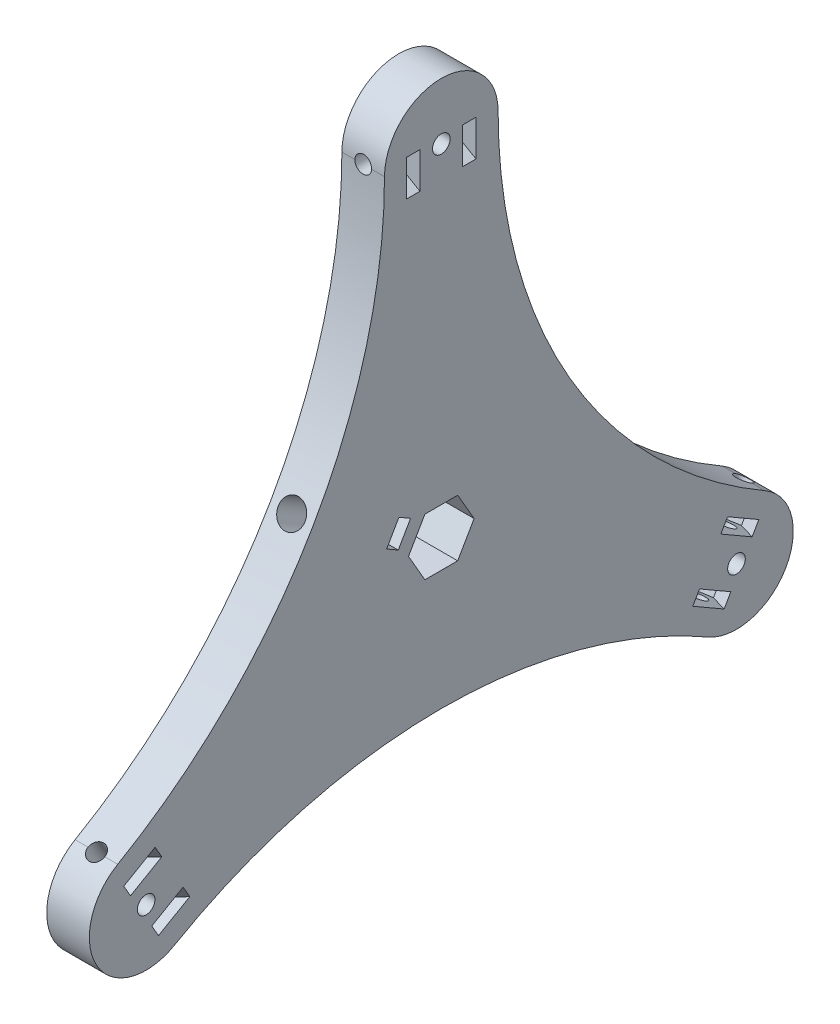
SolidWorks part; units mm, degrees
ref_plane "Front Plane" through (0, 0, 0) normal (0, 0, 1) x (1, 0, 0)
ref_plane "Top Plane" through (0, 0, 0) normal (0, 1, 0) x (1, 0, 0)
ref_plane "Right Plane" through (0, 0, 0) normal (1, 0, 0) x (0, 0, -1)
sketch "Sketch1" plane through (0, 0, 0) normal (1, 0, 0) x (0, 0, -1)
  line L0 (0, 0) -> (0, 76.2) construction
  line L1 (0, 0) -> (65.9911, -38.1) construction
  line L2 (0, 0) -> (-65.9911, -38.1) construction
  line L3 (-65.9911, -38.1) -> (0, 76.2) construction
  line L4 (0, 76.2) -> (65.9911, -38.1) construction
  line L5 (65.9911, -38.1) -> (-65.9911, -38.1) construction
  line L6 (-12.7, 76.2) -> (12.7, 76.2) construction
  line L8 (-3.6662, 6.35) -> (-7.3323, 0)
  line L9 (-7.3323, 0) -> (-3.6662, -6.35)
  line L10 (-3.6662, -6.35) -> (3.6662, -6.35)
  line L11 (3.6662, -6.35) -> (7.3323, 0)
  line L12 (7.3323, 0) -> (3.6662, 6.35)
  line L13 (3.6662, 6.35) -> (-3.6662, 6.35)
  circle A1 centre (0, 76.2) radius 1.9685
  circle A2 centre (65.9911, -38.1) radius 1.9685
  circle A3 centre (-65.9911, -38.1) radius 1.9685
  arc A4 (12.7, 76.2) -> (-12.7, 76.2) centre (0, 76.2) ccw
  arc A5 (59.6411, -49.0985) -> (72.3411, -27.1015) centre (65.9911, -38.1) ccw
  arc A6 (-72.3411, -27.1015) -> (-59.6411, -49.0985) centre (-65.9911, -38.1) ccw
  arc A7 (-12.7, 76.2) -> (-72.3411, -27.1015) centre (-131.9823, 76.2) cw
  arc A8 (12.7, 76.2) -> (72.3411, -27.1015) centre (131.9823, 76.2) ccw
  arc A9 (-59.6411, -49.0985) -> (59.6411, -49.0985) centre (0, -152.4) cw
  circle A10 centre (0, 0) radius 6.35 construction
  dimension "D1" = 12.7
  dimension "D2" = 3.937
  dimension "D4" = 25.4
  dimension "D3" = 76.2
extrude "Boss-Extrude1" add sketch "Sketch1" along normal blind 9.525 contours A6 A9 A5 A8 A4 A7 A1 A2 A3 region at (0, 15.5067, -26.8583)
sketch "Sketch3" plane through (0, 3.175, 5.4993) normal (0, -0.5, -0.866) x (-1, 0, 0)
  line L0 (-9.525, 0) -> (0, 0) construction
  line L4 (0, -3.6662) -> (0, 3.6662)
  line L5 (0, 3.6662) -> (-9.525, 3.6662)
  line L6 (-9.525, 3.6662) -> (-9.525, -3.6662)
  line L7 (-9.525, -3.6662) -> (0, -3.6662)
  line L8 (0, -3.6662) -> (0, 3.6662) construction
  line L9 (0, 3.6662) -> (-9.525, 3.6662) construction
  line L10 (-9.525, 3.6662) -> (-9.525, -3.6662) construction
  line L11 (-9.525, -3.6662) -> (0, -3.6662) construction
  circle A0 centre (-4.7625, 0) radius 1.6
  dimension "D2" = 3.2
  dimension "D1" = 0
extrude "Cut-Extrude1" cut sketch "Sketch3" against normal through all
sketch "Sketch4" plane through (0, 3.175, 5.4993) normal (0, -0.5, -0.866) x (-1, 0, 0)
  line L0 (-9.525, 0) -> (0, 0) construction
  line L1 (-3.1748, 2.75) -> (-6.3502, 2.75)
  line L2 (-6.3502, 2.75) -> (-7.9379, 0) construction
  line L3 (-7.9379, 0) -> (-6.3502, -2.75) construction
  line L4 (-6.3502, -2.75) -> (-3.1748, -2.75)
  line L5 (-3.1748, -2.75) -> (-1.5871, 0)
  line L6 (-1.5871, 0) -> (-3.1748, 2.75)
  line L7 (-6.3502, 2.75) -> (-9.525, 2.75)
  line L8 (-9.525, 3.6662) -> (-9.525, -3.6662) construction
  line L9 (-9.525, 2.75) -> (-9.525, -2.75)
  line L10 (-9.525, -2.75) -> (-6.3502, -2.75)
  circle A0 centre (-4.7625, 0) radius 2.75 construction
  dimension "D1" = 5.5
extrude "Cut-Extrude2" cut sketch "Sketch4" against normal blind 3 from offset 3.175 offset against normal yes
sketch "Sketch5" plane through (0, 6.2625, 10.847) normal (0, -0.5, -0.866) x (-1, 0, 0)
  circle A0 centre (-4.7625, 0) radius 3
  dimension "D1" = 6
extrude "Cut-Extrude3" cut sketch "Sketch5" against normal up to surface (15.868 mm away) from offset 4.7625 up to face at (4.3946, 15.2154, 29.4682) offset against normal yes
sketch "Sketch6" plane through (0, 0, 0) normal (0, 0, 1) x (1, 0, 0)
  line L0 (9.525, 76.2) -> (0, 76.2) construction
  line L1 (9.525, 74.2315) -> (9.525, 78.1685) construction
  line L2 (9.525, 74.2315) -> (9.525, 78.1685) construction
  line L3 (4.7625, 88.9) -> (4.7625, 71.7991) construction
  line L4 (9.525, 88.9) -> (0, 88.9) construction
  circle A0 centre (4.7625, 76.2) radius 1.875
  dimension "D1" = 3.75
extrude "Cut-Extrude4" cut sketch "Sketch6" against normal through all
sketch "Sketch7" plane through (0, 0, 0) normal (0, 0, 1) x (1, 0, 0)
  line L0 (8.2625, 78.2207) -> (9.525, 77.4918)
  line L1 (1.2625, 74.1793) -> (4.7625, 72.1585)
  line L2 (4.7625, 72.1585) -> (8.2625, 74.1793) construction
  line L3 (8.2625, 74.1793) -> (8.2625, 78.2207) construction
  line L4 (8.2625, 78.2207) -> (4.7625, 80.2415)
  line L5 (4.7625, 80.2415) -> (1.2625, 78.2207)
  line L6 (1.2625, 78.2207) -> (1.2625, 74.1793)
  line L7 (9.525, 74.2315) -> (9.525, 78.1685) construction
  line L8 (9.525, 77.4918) -> (9.525, 69.4089)
  line L9 (9.525, -27.1015) -> (9.525, 76.2) construction
  line L10 (4.7625, 72.1585) -> (9.525, 69.4089)
  circle A0 centre (4.7625, 76.2) radius 3.5 construction
  point P1 (9.525, 69.6478)
  dimension "D1" = 7
extrude "Cut-Extrude5" cut sketch "Sketch7" against normal blind 3 from offset 4.7625 offset against normal yes
mirror "Mirror1" about plane through (0, 0, 0) normal (0, 0, 1) of "Cut-Extrude5", "Cut-Extrude4"
ref_axis "Axis1" through (-0.4763, 0, 0) along (1, 0, 0)
pattern_circular "CirPattern1" count 3 over 360 about axis through (-0.4763, 0, 0) along (1, 0, 0) of "Cut-Extrude5", "Mirror1"
